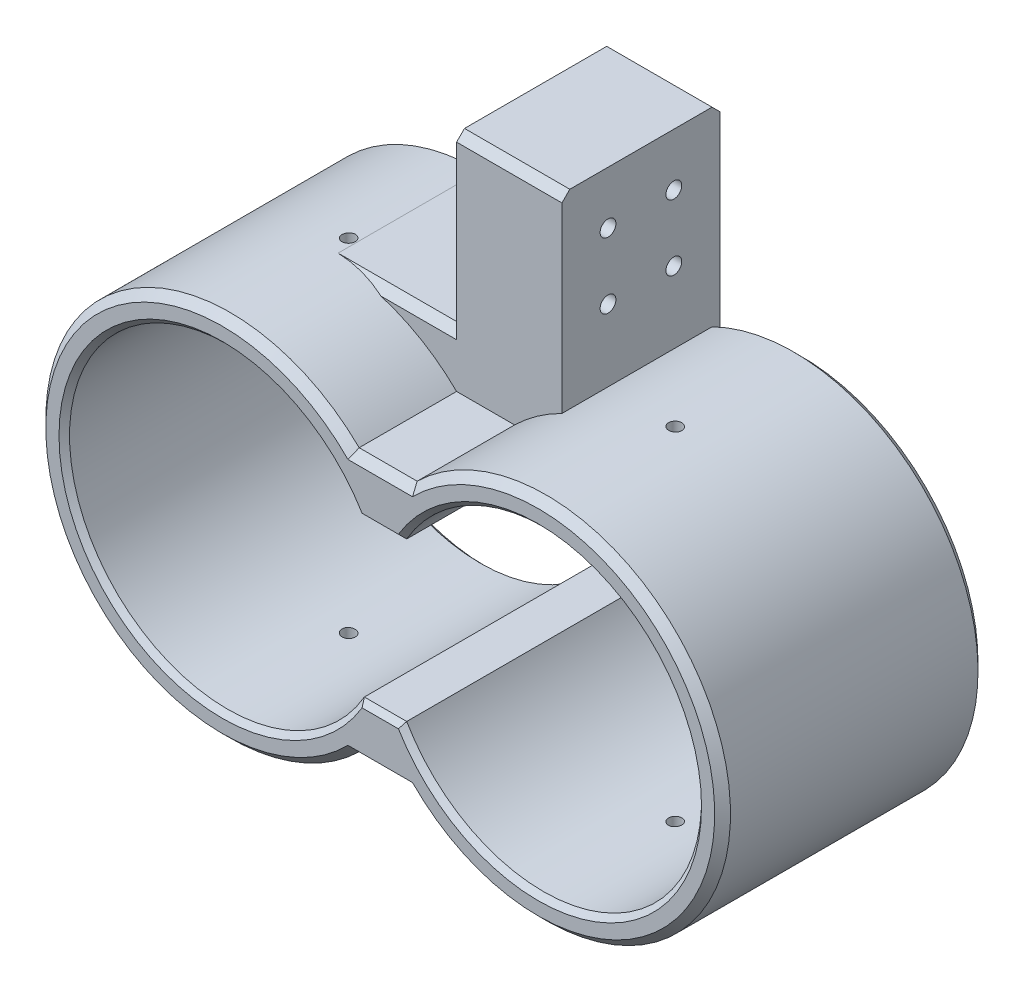
SolidWorks part; units mm, degrees
ref_plane "前视基准面" through (0, 0, 0) normal (0, 0, 1) x (1, 0, 0)
ref_plane "上视基准面" through (0, 0, 0) normal (0, 1, 0) x (1, 0, 0)
ref_plane "右视基准面" through (0, 0, 0) normal (1, 0, 0) x (0, 0, -1)
sketch "草图1" plane through (0, 0, 0) normal (0, 0, 1) x (1, 0, 0)
  line L0 (24.4949, -25) -> (35.5051, -25)
  line L2 (-34, 0) -> (97, 0) construction
  line L3 (24.4949, 25) -> (35.5051, 25)
  arc A0 (24.4949, 25) -> (24.4949, -25) centre (0, 0) ccw
  arc A1 (35.5051, -25) -> (35.5051, 25) centre (60, 0) ccw
  point P4 (0, 0)
  point P5 (0, 0)
  point P6 (0, 0)
  point P7 (0, 0)
  point P13 (0, 0)
  point P14 (0, 0)
  dimension "D1" = 70
  dimension "D2" = 70
  dimension "D3" = 60
  dimension "D4" = 50
extrude "凸台-拉伸1" add sketch "草图1" along normal blind 50
sketch "草图2" plane through (0, 0, 50) normal (0, 0, 1) x (1, 0, 0)
  line L0 (-30, 0) -> (90, 0) construction
  line L1 (25.9808, -15) -> (34.0192, -15)
  line L2 (25.9808, 15) -> (34.0192, 15)
  arc A0 (25.9808, 15) -> (25.9808, -15) centre (0, 0) ccw
  arc A1 (34.0192, -15) -> (34.0192, 15) centre (60, 0) ccw
  arc A2 (35.5051, -25) -> (35.5051, 25) centre (60, 0) ccw construction
  dimension "D1" = 60
  dimension "D2" = 60
  dimension "D3" = 30
extrude "切除-拉伸1" cut sketch "草图2" against normal through all
sketch "草图3" plane through (0, 0, 0) normal (0, 1, 0) x (1, 0, 0)
  line L0 (-35, -25) -> (95, -25) construction
  line L1 (-35, 0) -> (-35, -50) construction
  line L2 (95, -50) -> (95, 0) construction
  circle A0 centre (-1, -25) radius 1.25
  circle A1 centre (61, -25) radius 1.25
  point P10 (0, 0)
  dimension "D1" = 34
  dimension "D3" = 2.5
  dimension "D4" = 2.5
  dimension "D2" = 34
extrude "切除-拉伸2" cut sketch "草图3" against normal through all both and the other way through all
ref_plane "基准面4" through (0, 67.5, 0) normal (0, 1, 0) x (1, 0, 0)
sketch "草图4" plane through (0, 67.5, 0) normal (0, 1, 0) x (1, 0, 0)
  line L0 (95, 0) -> (35.5051, 0) construction
  line L1 (44.4949, 0) -> (24.4949, 0)
  line L2 (44.4949, 0) -> (44.4949, -30)
  line L3 (44.4949, -30) -> (24.4949, -30)
  line L4 (24.4949, 0) -> (24.4949, -30)
  line L5 (44.4949, 0) -> (24.4949, -30) construction
  line L6 (44.4949, -30) -> (24.4949, 0) construction
  line L8 (30, 0) -> (30, -49.9572) construction
  line L9 (35.5051, 0) -> (24.4949, 0) construction
  line L10 (24.4949, -50) -> (24.4949, 0) construction
  point P0 (34.4949, -15)
  point P11 (0, 0)
  dimension "D1" = 30
  dimension "D3" = 20
extrude "凸台-拉伸2" add sketch "草图4" against normal up to surface (42.5 mm away) up to face at (30, 25, 25)
sketch "草图5" plane through (44.4949, 0, 0) normal (1, 0, 0) x (0, 0, -1)
  line L0 (-15, 31.3782) -> (-15, 67.5) construction
  line L1 (0, 31.3782) -> (-30, 31.3782) construction
  line L2 (-30, 67.5) -> (0, 67.5) construction
  circle A0 centre (-21.25, 57.5) radius 1.5
  circle A1 centre (-8.75, 57.5) radius 1.5
  circle A2 centre (-8.75, 45) radius 1.5
  circle A3 centre (-21.25, 45) radius 1.5
  dimension "D1" = 3
  dimension "D2" = 12.5
  dimension "D3" = 12.5
  dimension "D4" = 12.5
  dimension "D5" = 10
extrude "切除-拉伸3" cut sketch "草图5" against normal up to next
sketch "草图6" plane through (0, 0, 0) normal (0, 0, -1) x (-1, 0, 0)
  circle A0 centre (-60, 0) radius 30
  arc A1 (-44.4949, 25.6825) -> (-34.0192, -15) centre (-60, 0) ccw construction
extrude "切除-拉伸4" cut sketch "草图6" against normal through all
ref_plane "基准面5" through (0, 35, 0) normal (0, 1, 0) x (1, 0, 0)
chamfer "倒角1" distance 1.5 angle 45 2 edges at (34.4949, 67.5, 30) (34.4949, 67.5, 0)
sketch "草图7" plane through (0, 35, 0) normal (0, 1, 0) x (1, 0, 0)
  line L1 (0.4949, -30) -> (24.4949, -30)
  line L2 (0.4949, -30) -> (0.4949, 0)
  line L3 (0.4949, 0) -> (24.4949, 0)
  line L4 (24.4949, -30) -> (24.4949, 0)
  line L5 (0.4949, -30) -> (24.4949, 0) construction
  line L6 (0.4949, 0) -> (24.4949, -30) construction
  line L8 (44.4949, -30) -> (24.4949, -30) construction
  line L14 (24.4949, -1.5) -> (24.4949, -28.5) construction
  line L15 (25.9808, 0) -> (34.0192, 0) construction
  point P0 (12.4949, -15)
  dimension "D1" = 24
extrude "凸台-拉伸3" add sketch "草图7" against normal up to surface (10 mm away) up to face at (30, 25, 40)
sketch "草图8" plane through (0, 0, 0) normal (0, 0, -1) x (-1, 0, 0)
  circle A0 centre (0, 0) radius 30
  arc A1 (-25.9808, -15) -> (-0.4949, 29.9959) centre (0, 0) ccw construction
extrude "切除-拉伸5" cut sketch "草图8" against normal through all
chamfer "倒角2" distance 1.5 angle 45 8 edges at (94.5634, -5.5113, 0) (30, 25, 50) (95, 0, 50) (30, -25, 50) (-35, 0, 50) (30, -25, 0) (12.4949, 35, 0) (12.4949, 35, 30)
chamfer "倒角3" distance 1 angle 45 8 edges at (30, -15, 50) (-30, 0, 50) (30, 15, 50) (90, 0, 50) (30, 15, 0) (-30, 0, 0) (30, -15, 0) (90, 0, 0)
chamfer "倒角4" distance 1.5 angle 45 1 edges at (-29.5748, -18.7172, 0)
